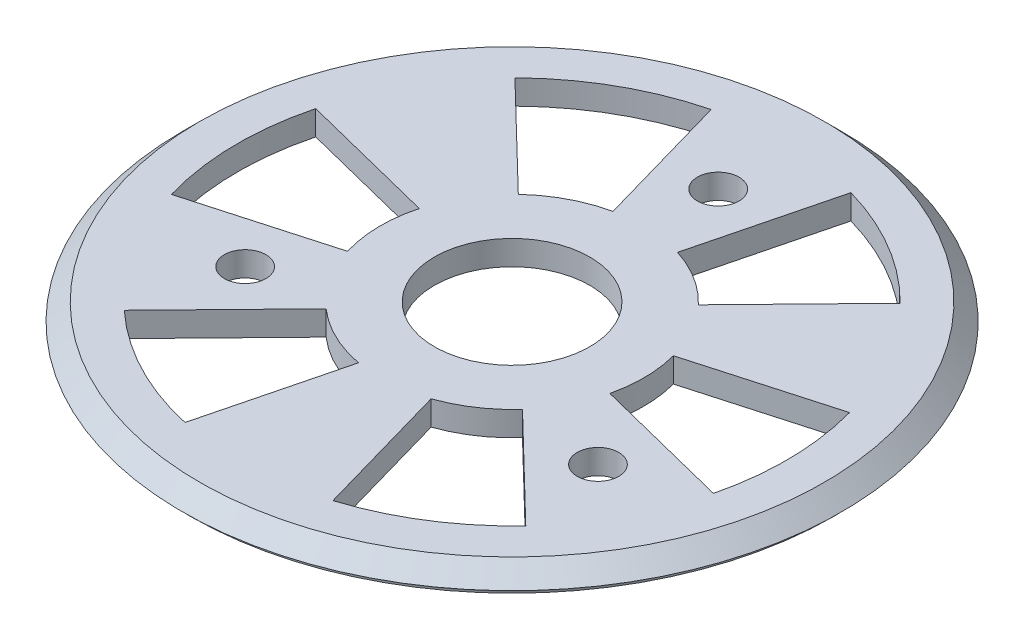
SolidWorks part; units mm, degrees
ref_plane "Front Plane" through (0, 0, 0) normal (0, 0, 1) x (1, 0, 0)
ref_plane "Top Plane" through (0, 0, 0) normal (0, 1, 0) x (1, 0, 0)
ref_plane "Right Plane" through (0, 0, 0) normal (1, 0, 0) x (0, 0, -1)
sketch "Sketch1" plane through (0, 0, 0) normal (0, 0, 1) x (1, 0, 0)
  line L0 (-3, 0) -> (2.8333, 0)
  line L1 (-3, -3) -> (0.175, -3)
  line L2 (-3, -3) -> (-3, 3)
  line L5 (-36.5367, 18.9165) -> (-36.5367, -17.1911)
  line L8 (3.7405, -0.9071) -> (0.175, -3)
  line L9 (3.7405, 0.9071) -> (1.6476, 3)
  line L10 (-3, 3) -> (1.6476, 3)
  arc A0 (3.7405, 0.9071) -> (3.7405, -0.9071) centre (3.7405, 0) ccw
  point P0 (0, 0)
  dimension "D3" = 135
  dimension "D4" = 0.9071
  dimension "D1" = 6
  dimension "D2" = 39.37
revolve "Revolve1" add sketch "Sketch1" angle 360 about L5 region at (-0.0774, 1.4404, 0)
sketch "Sketch2" plane through (0, 0, 0) normal (0, 1, 0) x (1, 0, 0)
  line L12 (-20.8677, -3.7179) -> (-3.8352, -7.9993)
  line L13 (-24.5315, -10.7339) -> (-11.9075, -22.9517)
  line L14 (-31.225, -15.2028) -> (-26.4115, -32.107)
  line L15 (-39.4735, -15.8339) -> (-43.7873, -32.8756)
  line L16 (-47.1675, -12.0965) -> (-59.4328, -24.6809)
  line L17 (-51.9399, -4.699) -> (-68.8408, -9.4775)
  line L18 (-52.0809, 4.2089) -> (-69.1149, 8.4873)
  line L19 (-47.5369, 11.7615) -> (-60.1695, 23.9764)
  line L20 (-39.9462, 15.7389) -> (-44.7647, 32.6447)
  line L21 (-31.6677, 15.3503) -> (-27.3586, 32.3904)
  line L22 (-24.8402, 11.0694) -> (-12.5835, 23.6563)
  line L23 (-20.9779, 4.1549) -> (-4.0792, 8.938)
  circle A19 centre (-36.5367, 0) radius 9.5
  arc A20 (-31.225, -15.2028) -> (-24.5315, -10.7339) centre (-36.5367, 0) ccw
  arc A24 (-20.8677, -3.7179) -> (-20.9779, 4.1549) centre (-36.5367, 0) ccw
  arc A25 (-24.8402, 11.0694) -> (-31.6677, 15.3503) centre (-36.5367, 0) ccw
  arc A26 (-39.9462, 15.7389) -> (-47.5369, 11.7615) centre (-36.5367, 0) ccw
  arc A27 (-52.0809, 4.2089) -> (-51.9399, -4.699) centre (-36.5367, 0) ccw
  arc A28 (-47.1675, -12.0965) -> (-39.4735, -15.8339) centre (-36.5367, 0) ccw
  arc A35 (-4.0792, 8.938) -> (-12.5835, 23.6563) centre (-36.5367, 0) ccw
  arc A36 (-27.3586, 32.3904) -> (-44.7647, 32.6447) centre (-36.5367, 0) ccw
  arc A37 (-60.1695, 23.9764) -> (-69.1149, 8.4873) centre (-36.5367, 0) ccw
  arc A38 (-68.8408, -9.4775) -> (-59.4328, -24.6809) centre (-36.5367, 0) ccw
  arc A39 (-43.7873, -32.8756) -> (-26.4115, -32.107) centre (-36.5367, 0) ccw
  arc A40 (-11.9075, -22.9517) -> (-3.8352, -7.9993) centre (-36.5367, 0) ccw
  dimension "D1" = 19
  dimension "D2" = 6.604
extrude "Boss-Extrude1" add sketch "Sketch2" along direction (0, 1, 0) on the side of the normal up to surface (3 mm away) contours L13 A40 L12 A24 L23 A35 L22 A25 L21 A36 L20 A26 L19 A37 L18 A27 L17 A38 L16 A28 L15 A39 L14 A20 | A19 up to face at (-74.721, 3, 0)
sketch "Sketch3" plane through (0, 3, 0) normal (0, 1, 0) x (1, 0, 0)
  circle A1 centre (-14.4513, 12.5808) radius 2.4765
  circle A3 centre (-35.151, -24.5318) radius 2.4765
  circle A5 centre (-56.9416, 11.951) radius 2.4765
  dimension "D1" = 4.953
  dimension "D3" = 4.953
  dimension "D2" = 4.953
sketch "Sketch5" plane through (0, 3, 0) normal (0, 1, 0) x (1, 0, 0)
  circle A0 centre (-35.8782, 24.5318) radius 2.54
  circle A1 centre (-14.0877, -11.951) radius 2.54
  circle A2 centre (-56.578, -12.5808) radius 2.54
extrude "Boss-Extrude2" add sketch "Sketch3" against normal blind 6 contours A3 | A5 | A1 region at (-35.151, 3, 24.5318)
extrude "Cut-Extrude1" cut sketch "Sketch5" against normal up to surface (3 mm away) up to face at (-16.9278, 0, -12.5808)
